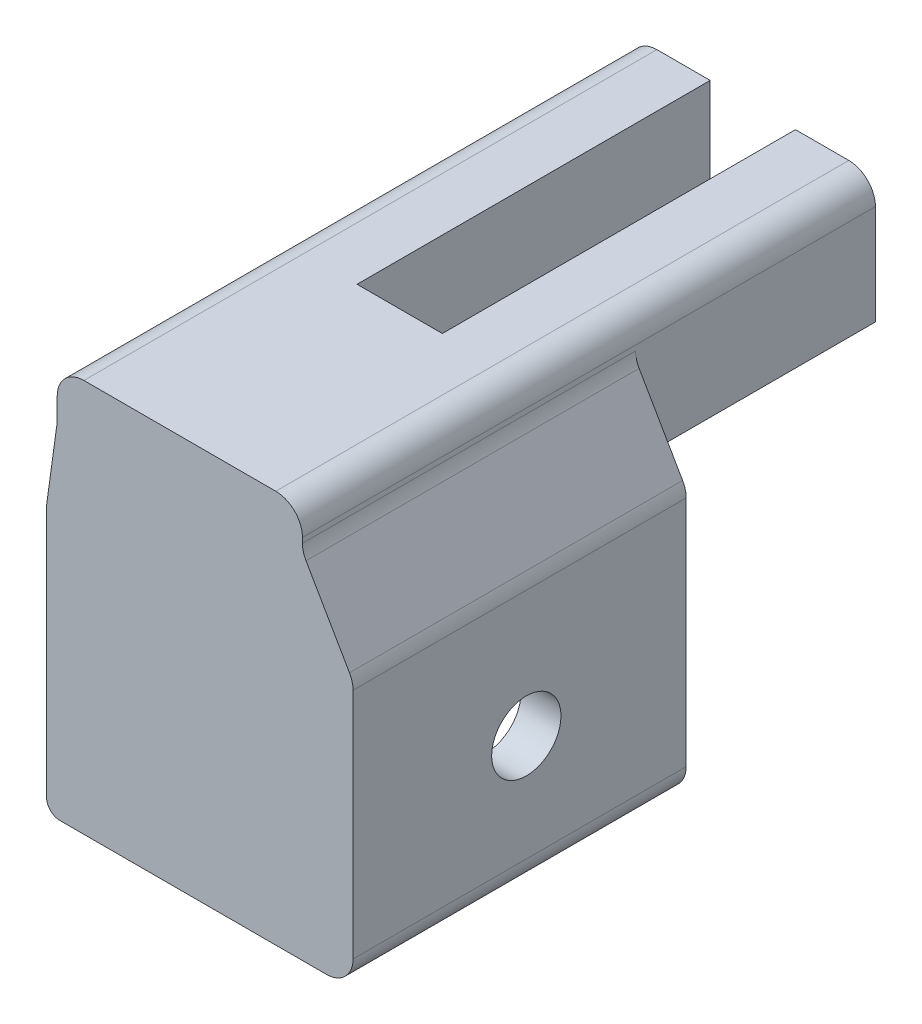
SolidWorks part; units mm, degrees
ref_plane "正面" through (0, 0, 0) normal (0, 0, 1) x (1, 0, 0)
ref_plane "平面" through (0, 0, 0) normal (0, 1, 0) x (1, 0, 0)
ref_plane "右側面" through (0, 0, 0) normal (1, 0, 0) x (0, 0, -1)
sketch "ｽｹｯﾁ1" plane through (0, 0, 0) normal (0, 0, 1) x (1, 0, 0)
  line L1 (-10, 10) -> (10, 10)
  line L2 (-10, 10) -> (-10, -10)
  line L3 (-10, -10) -> (10, -10)
  line L4 (10, 10) -> (10, -10)
  line L5 (-10, 10) -> (10, -10) construction
  line L6 (-10, -10) -> (10, 10) construction
  point P0 (0, 0)
  dimension "D1" = 20
extrude "ﾎﾞｽ - 押し出し1" add sketch "ｽｹｯﾁ1" along normal blind 3
sketch "ｽｹｯﾁ2" plane through (0, 0, 0) normal (0, 0, -1) x (-1, 0, 0)
  line L0 (-10, 10) -> (10, 10) construction
  line L1 (-3, 3.5) -> (3, 3.5)
  line L2 (-3, 3.5) -> (-3, 10)
  line L3 (-3, 10) -> (3, 10)
  line L4 (3, 3.5) -> (3, 10)
  line L5 (-3, 3.5) -> (3, 10) construction
  line L6 (-3, 10) -> (3, 3.5) construction
  line L7 (0, 0) -> (0, 6.75) construction
  point P0 (0, 6.75)
  dimension "D1" = 6.5
  dimension "D2" = 6
extrude "ﾎﾞｽ - 押し出し2" add sketch "ｽｹｯﾁ2" along normal blind 40
sketch "ｽｹｯﾁ3" plane through (0, 0, 3) normal (0, 0, 1) x (1, 0, 0)
  line L0 (-10, -10) -> (10, -10) construction
  line L1 (10, 10) -> (13, 10)
  line L2 (10, 10) -> (10, -10)
  line L3 (10, -10) -> (13, -10)
  line L4 (13, 10) -> (13, -10)
  dimension "D1" = 3
extrude "ﾎﾞｽ - 押し出し3" add sketch "ｽｹｯﾁ3" against normal blind 25
sketch "ｽｹｯﾁ4" plane through (13, 0, 0) normal (1, 0, 0) x (0, 0, -1)
  line L0 (0, 0) -> (22, 0) construction
  line L1 (22, -10) -> (22, 10) construction
  circle A0 centre (10, 0) radius 2.6
  dimension "D1" = 10
  dimension "D2" = 5.2
extrude "ｶｯﾄ - 押し出し1" cut sketch "ｽｹｯﾁ4" against normal up to next
fillet "ﾌｨﾚｯﾄ1" radius 1 1 edges at (-10, -10, 1.5)
ref_plane "平面1" through (0, 0, -13.5) normal (0, 0, -1) x (-1, 0, 0)
sketch "ｽｹｯﾁ5" plane through (0, 0, -13.5) normal (0, 0, -1) x (-1, 0, 0)
  line L0 (3, 10) -> (-3, 10) construction
  line L1 (-1.6, 5.5) -> (1.6, 5.5)
  line L2 (-1.6, 5.5) -> (-1.6, 10)
  line L3 (-1.6, 10) -> (1.6, 10)
  line L4 (1.6, 5.5) -> (1.6, 10)
  line L5 (-1.6, 5.5) -> (1.6, 10) construction
  line L6 (-1.6, 10) -> (1.6, 5.5) construction
  line L7 (0, 7.75) -> (0, 0) construction
  point P0 (0, 7.75)
  dimension "D1" = 3.2
  dimension "D2" = 4.5
extrude "ｶｯﾄ - 押し出し2" cut sketch "ｽｹｯﾁ5" along normal blind 30
sketch "ｽｹｯﾁ6" plane through (0, 0, 3) normal (0, 0, 1) x (1, 0, 0)
  line L0 (13, 10) -> (-10, 10) construction
  line L1 (3.2, 10) -> (9.2, 10)
  line L2 (3.2, 10) -> (3.2, 19.5)
  line L3 (3.2, 19.5) -> (9.2, 19.5)
  line L4 (9.2, 10) -> (9.2, 19.5)
  line L5 (0, 0) -> (0, 10) construction
  line L6 (-3.2, 19.5) -> (-9.2, 19.5)
  line L7 (-9.2, 10) -> (-9.2, 19.5)
  line L8 (-3.2, 10) -> (-9.2, 10)
  line L9 (-3.2, 10) -> (-3.2, 19.5)
  dimension "D1" = 6.4
  dimension "D2" = 9.5
  dimension "D3" = 6
extrude "ﾎﾞｽ - 押し出し4" add sketch "ｽｹｯﾁ6" against normal up to surface (43 mm away) up to face at (0, 7.25, -40)
sketch "ｽｹｯﾁ7" plane through (0, 0, 3) normal (0, 0, 1) x (1, 0, 0)
  line L1 (-3.2, 19.5) -> (3.2, 19.5)
  line L2 (-3.2, 19.5) -> (-3.2, 10)
  line L3 (-3.2, 10) -> (3.2, 10)
  line L4 (3.2, 19.5) -> (3.2, 10)
extrude "ﾎﾞｽ - 押し出し5" add sketch "ｽｹｯﾁ7" against normal blind 16.5
sketch "ｽｹｯﾁ8" plane through (0, 0, 3) normal (0, 0, 1) x (1, 0, 0)
  line L0 (13, 10) -> (9.2, 16.5818)
  line L1 (9.2, 10) -> (9.2, 19.5) construction
  line L2 (9.2, 16.5818) -> (9.2, 10)
  line L3 (9.2, 10) -> (13, 10)
  dimension "D1" = 60
extrude "ﾎﾞｽ - 押し出し6" add sketch "ｽｹｯﾁ8" against normal up to surface (25 mm away) up to face at (11.5, 0, -22)
fillet "ﾌｨﾚｯﾄ2" radius 2 5 edges at (13, -10, -9.5) (13, 10, -9.5) (9.2, 16.5818, -9.5) (9.2, 19.5, -18.5) (-9.2, 19.5, -18.5)
sketch "ｽｹｯﾁ9" plane through (0, 0, 3) normal (0, 0, 1) x (1, 0, 0)
  line L0 (-10, 10) -> (-9.2, 15.8)
  line L1 (-9.2, 17.5) -> (-9.2, 10) construction
  line L2 (-9.2, 15.8) -> (-9.2, 10)
  line L3 (-9.2, 10) -> (-10, 10)
  dimension "D1" = 5.8
extrude "ﾎﾞｽ - 押し出し7" add sketch "ｽｹｯﾁ9" against normal up to surface (43 mm away) up to face at (0, 7.25, -40)
sketch "ｽｹｯﾁ10" plane through (0, 0, -40) normal (0, 0, -1) x (-1, 0, 0)
  line L0 (3, 3.5) -> (3, 10) construction
  line L1 (1.6, 5.5) -> (3, 5.5)
  line L2 (1.6, 5.5) -> (1.6, 7.5)
  line L3 (1.6, 7.5) -> (3, 7.5)
  line L4 (3, 5.5) -> (3, 7.5)
  dimension "D1" = 2
extrude "ｶｯﾄ - 押し出し3" cut sketch "ｽｹｯﾁ10" against normal up to surface (26.5 mm away) up to face at (0, 11, -13.5)
fillet "ﾌｨﾚｯﾄ3" radius 0.5 2 edges at (-3, 7.5, -26.75) (-3, 5.5, -26.75)
fillet "ﾌｨﾚｯﾄ4" radius 1.5 2 edges at (3, 3.5, -20) (-3, 3.5, -20)
sketch "ｽｹｯﾁ12" plane through (0, 0, -40) normal (0, 0, -1) x (-1, 0, 0)
  line L4 (1.6, 7.5) -> (2.5, 7.5)
  line L5 (3, 8) -> (3, 10)
  line L6 (3, 10) -> (1.6, 10)
  line L7 (1.6, 10) -> (1.6, 7.5)
  line L8 (1.6, 7.5) -> (2.5, 7.5)
  line L9 (3, 8) -> (3, 10)
  line L10 (3, 10) -> (1.6, 10)
  line L11 (1.6, 10) -> (1.6, 7.5)
  arc A1 (2.5, 7.5) -> (3, 8) centre (2.5, 8) ccw
  arc A2 (2.5, 7.5) -> (3, 8) centre (2.5, 8) ccw
  dimension "D1" = 0
extrude "ｶｯﾄ - 押し出し4" cut sketch "ｽｹｯﾁ12" against normal up to surface (26.5 mm away) up to face at (-0.8005, 9.8571, -13.5)
